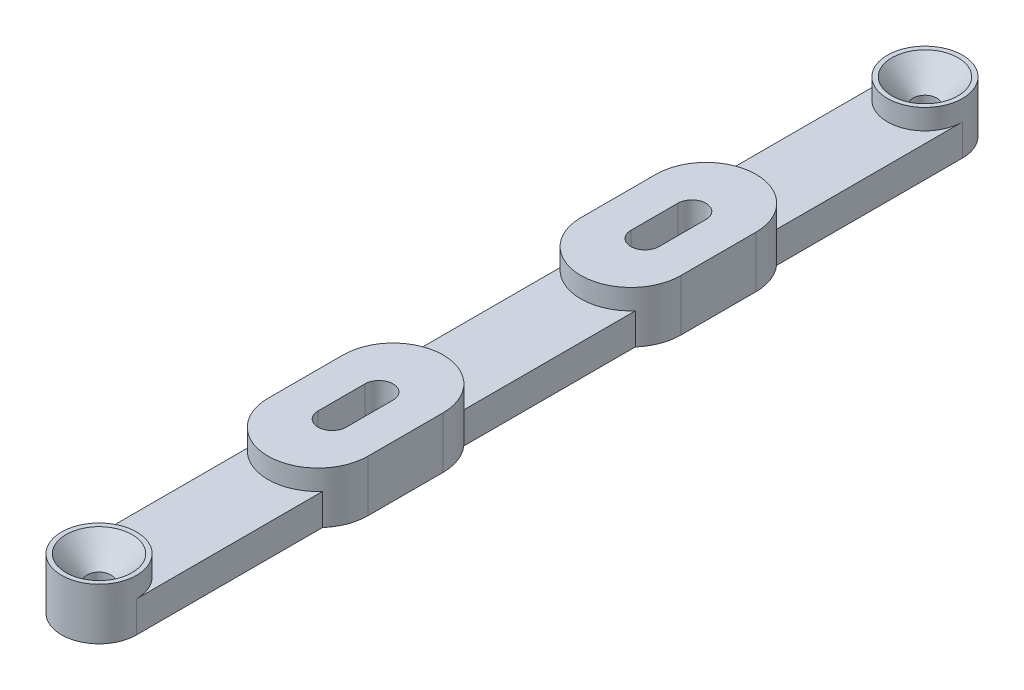
SolidWorks part; units mm, degrees
ref_plane "Front Plane" through (0, 0, 0) normal (0, 0, 1) x (1, 0, 0)
ref_plane "Top Plane" through (0, 0, 0) normal (0, 1, 0) x (1, 0, 0)
ref_plane "Right Plane" through (0, 0, 0) normal (1, 0, 0) x (0, 0, -1)
sketch "Arm Base Sketch" plane through (0, 0, 0) normal (0, 1, 0) x (1, 0, 0)
  line L0 (-6, 66) -> (6, 66)
  line L1 (6, 66) -> (6, 0)
  line L2 (6, 0) -> (-6, 0)
  line L3 (-6, 0) -> (-6, 66)
  point P2 (0, 0)
  dimension "D1" = 66
  dimension "D2" = 12
extrude "Arm Base Extrude" add sketch "Arm Base Sketch" along normal blind 5
sketch "Screw Bases Sketch" plane through (0, 0, 0) normal (0, -1, 0) x (1, 0, 0)
  line L0 (6, -66) -> (-6, -66) construction
  line L1 (0, -31) -> (0, -19) construction
  line L2 (-8, -31) -> (-8, -19)
  line L3 (8, -31) -> (8, -19)
  circle A0 centre (0, -66) radius 6
  arc A1 (-8, -31) -> (8, -31) centre (0, -31) ccw
  arc A2 (8, -19) -> (-8, -19) centre (0, -19) ccw
  point P8 (0, -25)
  dimension "D1" = 16
  dimension "D2" = 12
  dimension "Connector Screw Position" = 25
extrude "Screw Bases Extrude" add sketch "Screw Bases Sketch" against normal blind 8.25
hole_wizard "Power Supply Mounting Slot" positions "Power Supply Mounting Slot Position Sketch" profile "Power Supply Mounting Slot Profile Sketch" size "M4" standard "ANSI Metric" slot yes end condition through all
sketch "Power Supply Mounting Slot Position Sketch" plane through (0, 0, 0) normal (0, -1, 0) x (-1, 0, 0)
  line L0 (0, 31) -> (0, 19) construction
  line L1 (0, 31) -> (0, 19) construction
  point P0 (0, 25)
sketch "Power Supply Mounting Slot Profile Sketch" plane through (0, 0, -25) normal (1, 0, 0) x (0, 0, -1)
  line L0 (0, 0) -> (0, 8.25)
  line L1 (0, 8.25) -> (2.25, 8.25)
  line L3 (2.25, 8.25) -> (2.25, 3.1)
  line L4 (2.25, 3.1) -> (4.5, 3.1)
  line L5 (4.5, 3.1) -> (4.5, 0)
  line L7 (4.5, 0) -> (0, 0)
  line L11 (0, -6.35) -> (0, 107.95) construction
  dimension "Thru Hole Dia." = 4.5
  dimension "Thru Hole Depth" = 8.25
  dimension "C'Bore Dia." = 9
  dimension "C'Bore Depth" = 3.1
hole_wizard "No. 6 Mounting Screws" positions "No. 6 Mounting Screws Position Sketch" profile "No. 6 Mounting Screws Profile Sketch" countersink size "#6" standard "ANSI Inch" end condition through all
sketch "No. 6 Mounting Screws Position Sketch" plane through (0, 8.25, 0) normal (0, 1, 0) x (1, 0, 0)
  circle A0 centre (0, 66) radius 6 construction
  point P0 (0, 66)
sketch "No. 6 Mounting Screws Profile Sketch" plane through (0, 8.25, -66) normal (1, 0, 0) x (0, 0, 1)
  line L0 (0, 0) -> (0, 8.25)
  line L1 (0, 8.25) -> (1.8986, 8.25)
  line L2 (1.8986, 8.25) -> (1.8986, 3.8919)
  line L3 (1.8986, 3.8919) -> (5.2819, 0)
  line L5 (5.2819, 0) -> (0, 0)
  line L6 (-1.8987, 3.8919) -> (-5.2819, 0) construction
  line L11 (0, -6.35) -> (0, 107.95) construction
  dimension "Thru Hole Dia." = 3.7973
  dimension "Thru Hole Depth" = 8.25
  dimension "Near C'Sink Dia." = 10.5637
  dimension "Near C'Sink Angle" = 82
mirror "Mirror" about plane through (6, 5, 0) normal (0, 0, -1) of bodies 104
